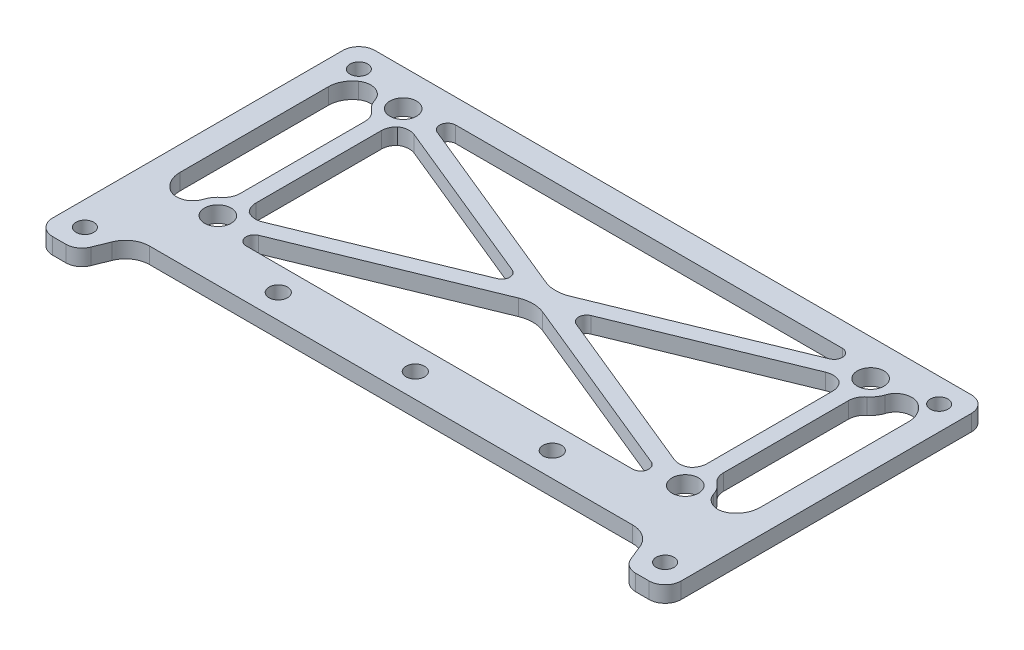
SolidWorks part; units mm, degrees
ref_plane "前视基准面" through (0, 0, 0) normal (0, 0, 1) x (1, 0, 0)
ref_plane "上视基准面" through (0, 0, 0) normal (0, 1, 0) x (1, 0, 0)
ref_plane "右视基准面" through (0, 0, 0) normal (1, 0, 0) x (0, 0, -1)
sketch "草图1" plane through (0, 0, 0) normal (0, 1, 0) x (1, 0, 0)
  line L1 (-39, 20) -> (39, 20)
  line L2 (-39, 20) -> (-39, -20)
  line L3 (-39, -20) -> (39, -20)
  line L4 (39, 20) -> (39, -20)
  line L5 (0, -20) -> (0, 20) construction
  line L6 (-39, 0) -> (39, 0) construction
  circle A0 centre (-36, 17) radius 1.1
  circle A1 centre (36, 17) radius 1.1
  circle A2 centre (36, -17) radius 1.1
  circle A3 centre (-36, -17) radius 1.1
  point P0 (0, 0)
  dimension "D1" = 2.2
  dimension "D2" = 72
  dimension "D3" = 34
  dimension "D4" = 78
  dimension "D5" = 40
extrude "凸台-拉伸1" add sketch "草图1" along normal blind 2
sketch "草图2" plane through (0, 2, 0) normal (0, 1, 0) x (1, 0, 0)
  line L0 (0, 28.5193) -> (0, -32.8374) construction
  line L1 (-47.1776, 0) -> (48.8533, 0) construction
  line L2 (-28.1648, 4) -> (28.6804, 4) construction
  circle A0 centre (-29, 15.5) radius 1.65
  circle A1 centre (29, 15.5) radius 1.65
  circle A2 centre (29, -7.5) radius 1.65
  circle A3 centre (-29, -7.5) radius 1.65
  dimension "D1" = 3.3
  dimension "D2" = 23
  dimension "D3" = 58
  dimension "D4" = 4
extrude "切除-拉伸1" cut sketch "草图2" against normal through all
sketch "草图3" plane through (0, 2, 0) normal (0, 1, 0) x (1, 0, 0)
  line L0 (0, 28.8147) -> (0, -28.8147) construction
  line L1 (-26.7164, 13.8797) -> (-2.6347, 4)
  line L2 (-29, -7.5) -> (29, -7.5) construction
  line L7 (-39, -12) -> (39, -12) construction
  line L8 (-39, 20) -> (-39, -20) construction
  line L9 (39, -20) -> (39, 20) construction
  line L10 (-39, -12) -> (39, 20) construction
  line L11 (39, -12) -> (-39, 20) construction
  line L12 (-24.3602, 15.0748) -> (0, 5.0809)
  line L13 (0, 5.0809) -> (24.3602, 15.0748)
  line L14 (23.9807, 17) -> (-23.9807, 17)
  line L15 (39, 20) -> (-39, 20) construction
  line L16 (-39, 4) -> (39, 4) construction
  line L17 (-31.8613, 15.9904) -> (-31.7636, 15.9503)
  line L18 (-2.6347, 4) -> (-26.7164, -5.8797)
  line L19 (-36, -5.2149) -> (-36, 13.2149)
  line L20 (0, 2.9191) -> (24.3602, -7.0748)
  line L21 (-24.3602, -7.0748) -> (0, 2.9191)
  line L22 (23.9807, -9) -> (-23.9807, -9)
  line L23 (2.6347, 4) -> (26.7164, -5.8797)
  line L24 (31.8613, 15.9904) -> (31.7636, 15.9503)
  line L25 (36, -5.2149) -> (36, 13.2149)
  line L26 (-31.7636, 15.9503) -> (-26.7164, 13.8797) construction
  line L27 (26.7164, 13.8797) -> (2.6347, 4)
  line L28 (31.7636, 15.9503) -> (26.7164, 13.8797) construction
  line L29 (31.7636, -7.9503) -> (31.8613, -7.9904)
  line L30 (26.7164, -5.8797) -> (31.7636, -7.9503) construction
  line L31 (-31.7636, -7.9503) -> (-31.8613, -7.9904)
  line L32 (-26.7164, -5.8797) -> (-31.7636, -7.9503) construction
  arc A0 (31.7636, 15.9503) -> (26.7164, 13.8797) centre (29, 15.5) cw
  arc A1 (-24.3602, -7.0748) -> (-23.9807, -9) centre (-23.9807, -8) ccw
  arc A2 (24.3602, -7.0748) -> (23.9807, -9) centre (23.9807, -8) cw
  arc A3 (24.3602, 15.0748) -> (23.9807, 17) centre (23.9807, 16) ccw
  arc A4 (-24.3602, 15.0748) -> (-23.9807, 17) centre (-23.9807, 16) cw
  arc A5 (31.8613, -7.9904) -> (36, -5.2149) centre (33, -5.2149) ccw
  arc A6 (-31.8613, -7.9904) -> (-36, -5.2149) centre (-33, -5.2149) cw
  arc A7 (31.8613, 15.9904) -> (36, 13.2149) centre (33, 13.2149) cw
  arc A8 (-31.8613, 15.9904) -> (-36, 13.2149) centre (-33, 13.2149) ccw
  arc A9 (31.7636, -7.9503) -> (26.7164, -5.8797) centre (29, -7.5) ccw
  arc A10 (-31.7636, -7.9503) -> (-26.7164, -5.8797) centre (-29, -7.5) cw
  arc A11 (-31.7636, 15.9503) -> (-26.7164, 13.8797) centre (-29, 15.5) ccw
  point P26 (0, 4)
  point P47 (-29.0528, -9)
  point P50 (29.0528, -9)
  point P53 (29.0528, 17)
  point P56 (-29.0528, 17)
  point P59 (36, -9.6883)
  point P62 (-36, -9.6883)
  point P65 (36, 17.6883)
  point P68 (-36, 17.6883)
  dimension "D6" = 1
  dimension "D7" = 3
  dimension "D8" = 2.8
  dimension "D9" = 2.8
  dimension "D10" = 2.8
  dimension "D11" = 2.8
  dimension "D1" = 4.5
  dimension "D2" = 3
  dimension "D3" = 3
  dimension "D4" = 1
  dimension "D5" = 1
extrude "切除-拉伸2" cut sketch "草图3" against normal through all
sketch "草图4" plane through (0, 2, 0) normal (0, 1, 0) x (1, 0, 0)
  line L0 (0, 32.0573) -> (0, -34.2728) construction
  line L1 (-34, -20) -> (-32, -15)
  line L2 (-39, -20) -> (39, -20) construction
  line L3 (-32, -15) -> (32, -15)
  line L4 (-34, -20) -> (34, -20)
  line L5 (34, -20) -> (32, -15)
  point P10 (0, -20)
  point P11 (0, -15)
  dimension "D1" = 34
  dimension "D2" = 32
  dimension "D3" = 5
extrude "切除-拉伸3" cut sketch "草图4" against normal through all
sketch "草图5" plane through (0, 2, 0) normal (0, 1, 0) x (1, 0, 0)
  line L0 (0, 38.9119) -> (0, -37.2684) construction
  line L1 (-30, 13.4615) -> (-30, -5.4566)
  line L2 (-30, 13.4615) -> (-28, 13.4615)
  line L3 (-30, -5.4566) -> (-28, -5.4566)
  line L4 (-28, -5.4566) -> (-28, 13.4615)
  line L5 (-29, 13.4615) -> (-29, -5.4566) construction
  line L6 (29, 13.4615) -> (29, -5.4566) construction
  line L7 (30, -5.4566) -> (28, -5.4566)
  line L8 (30, 13.4615) -> (30, -5.4566)
  line L9 (30, 13.4615) -> (28, 13.4615)
  line L10 (28, -5.4566) -> (28, 13.4615)
  dimension "D1" = 2
  dimension "D2" = 58
extrude "凸台-拉伸2" add sketch "草图5" against normal up to surface (2 mm away) up to face at (-28.7159, 0, -4)
sketch "草图6" plane through (0, 2, 0) normal (0, 1, 0) x (1, 0, 0)
  line L0 (0, 29.1906) -> (0, -30.3722) construction
  line L1 (-37.1402, -12) -> (35.8876, -12) construction
  line L2 (32, -15) -> (-32, -15) construction
  circle A0 centre (0, -12) radius 1.15
  circle A1 centre (-17, -12) radius 1.15
  circle A2 centre (17, -12) radius 1.15
  point P13 (-16.5601, -12)
  dimension "D2" = 2.3
  dimension "D3" = 2.3
  dimension "D4" = 34
  dimension "D1" = 3
extrude "切除-拉伸4" cut sketch "草图6" against normal blind 10
fillet "圆角1" radius 2 8 edges at (31.7636, 1, 7.9503) (26.7164, 1, 5.8797) (26.7164, 1, -13.8797) (31.7636, 1, -15.9503) (-31.7636, 1, 7.9503) (-26.7164, 1, 5.8797) (-26.7164, 1, -13.8797) (-31.7636, 1, -15.9503)
fillet "圆角3" radius 1 2 edges at (2.6347, 1, -4) (-2.6347, 1, -4)
fillet "圆角4" radius 4 2 edges at (0, 1, -2.9191) (0, 1, -5.0809)
fillet "圆角5" radius 2 6 edges at (39, 1, -20) (34, 1, 20) (39, 1, 20) (-39, 1, -20) (-39, 1, 20) (-34, 1, 20)
fillet "圆角6" radius 3 2 edges at (32, 1, 15) (-32, 1, 15)
fillet "圆角7" radius 2 8 edges at (28, 1, 4.8847) (30, 1, 4.8847) (30, 1, -12.8847) (28, 1, -12.8847) (-30, 1, 4.8847) (-28, 1, 4.8847) (-28, 1, -12.8847) (-30, 1, -12.8847)
equation "\"m\"= 2"
